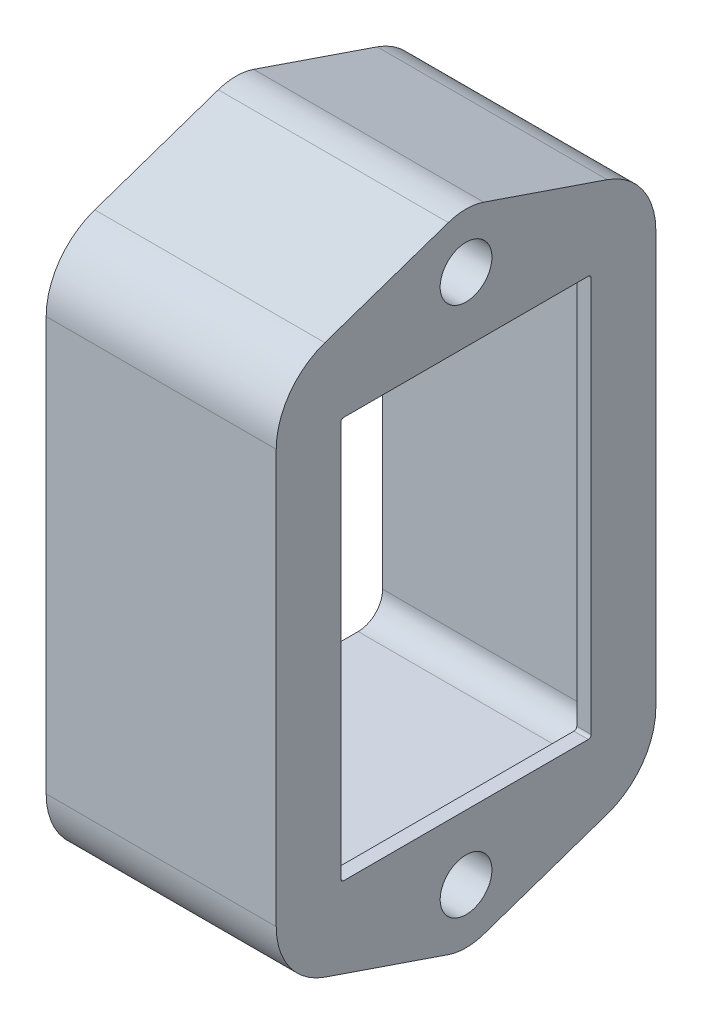
SolidWorks part; units mm, degrees
ref_plane "Alzado" through (0, 0, 0) normal (0, 0, 1) x (1, 0, 0)
ref_plane "Planta" through (0, 0, 0) normal (0, 1, 0) x (1, 0, 0)
ref_plane "Vista lateral" through (0, 0, 0) normal (1, 0, 0) x (0, 0, -1)
sketch "Croquis2" plane through (0, 0, 0) normal (1, 0, 0) x (0, 0, -1)
  line L0 (0, -55.062) -> (0, 49.3875) construction
  line L1 (-26.4, -41.4649) -> (-26.4, 16.0397)
  line L2 (-19.6372, 25.5012) -> (-2.4603, 31.3781)
  line L3 (19.6372, 25.5012) -> (2.4603, 31.3781)
  line L4 (26.4, -41.4649) -> (26.4, 16.0397)
  line L5 (19.6372, -50.9265) -> (2.4603, -56.8034)
  line L6 (20, -40.2126) -> (20, 14.7874) construction
  line L7 (17, 17.7874) -> (0, 17.7874) construction
  line L8 (0, 17.7874) -> (-17, 17.7874) construction
  line L9 (-20, 14.7874) -> (-20, -40.2126) construction
  line L10 (-17, -43.2126) -> (0, -43.2126) construction
  line L11 (0, -43.2126) -> (17, -43.2126) construction
  line L12 (20.4, -40.2126) -> (20.4, 14.7874)
  line L13 (17, 18.1874) -> (0, 18.1874)
  line L14 (0, 18.1874) -> (-17, 18.1874)
  line L15 (-20.4, 14.7874) -> (-20.4, -40.2126)
  line L16 (-17, -43.6126) -> (0, -43.6126)
  line L17 (0, -43.6126) -> (17, -43.6126)
  line L18 (-19.6372, -50.9265) -> (-2.4603, -56.8034)
  line L19 (-39.7632, -12.7126) -> (39.8458, -12.7126) construction
  circle A0 centre (0, 24.1874) radius 3.6
  arc A1 (2.4603, 31.3781) -> (-2.4603, 31.3781) centre (0, 24.1874) ccw
  arc A2 (-19.6372, 25.5012) -> (-26.4, 16.0397) centre (-16.4, 16.0397) ccw
  arc A3 (19.6372, 25.5012) -> (26.4, 16.0397) centre (16.4, 16.0397) cw
  arc A4 (20, 14.7874) -> (17, 17.7874) centre (17, 14.7874) ccw construction
  arc A5 (-17, 17.7874) -> (-20, 14.7874) centre (-17, 14.7874) ccw construction
  arc A6 (-20, -40.2126) -> (-17, -43.2126) centre (-17, -40.2126) ccw construction
  arc A7 (17, -43.2126) -> (20, -40.2126) centre (17, -40.2126) ccw construction
  arc A8 (20.4, 14.7874) -> (17, 18.1874) centre (17, 14.7874) ccw
  arc A9 (-17, 18.1874) -> (-20.4, 14.7874) centre (-17, 14.7874) ccw
  arc A10 (-20.4, -40.2126) -> (-17, -43.6126) centre (-17, -40.2126) ccw
  arc A11 (17, -43.6126) -> (20.4, -40.2126) centre (17, -40.2126) ccw
  circle A12 centre (0, -49.6126) radius 3.6
  arc A13 (2.4603, -56.8034) -> (-2.4603, -56.8034) centre (0, -49.6126) cw
  arc A14 (19.6372, -50.9265) -> (26.4, -41.4649) centre (16.4, -41.4649) ccw
  arc A15 (-19.6372, -50.9265) -> (-26.4, -41.4649) centre (-16.4, -41.4649) cw
  point P36 (-20.4, -12.7126)
  point P43 (-26.4, 23.1874)
  point P53 (26.4, -12.7126)
  point P58 (-26.4, -12.7126)
  dimension "D5" = 7.2
  dimension "D2" = 4
  dimension "D7" = 10
  dimension "D3" = 6
  dimension "D4" = 6
  dimension "D6" = 5
  dimension "D1" = 0.4
extrude "Saliente-Extruir1" add sketch "Croquis2" against normal blind 30 and the other way blind 2
sketch "Croquis3" plane through (2, 0, 0) normal (1, 0, 0) x (0, 0, -1)
  line L0 (-17, -43.6126) -> (17, -43.6126) construction
  line L1 (20.4, -40.2126) -> (20.4, 14.7874) construction
  line L2 (-20.4, 14.7874) -> (-20.4, -40.2126) construction
  line L3 (17, 18.1874) -> (-17, 18.1874) construction
  line L4 (-17, -43.6126) -> (17, -43.6126)
  line L5 (20.4, -40.2126) -> (20.4, 14.7874)
  line L6 (-20.4, 14.7874) -> (-20.4, -40.2126)
  line L7 (17, 18.1874) -> (-17, 18.1874)
  line L8 (-17, -40.6126) -> (17, -40.6126)
  line L9 (17.4, -40.2126) -> (17.4, 14.7874)
  line L10 (17, 15.1874) -> (-17, 15.1874)
  line L11 (-17.4, 14.7874) -> (-17.4, -40.2126)
  arc A0 (-20.4, -40.2126) -> (-17, -43.6126) centre (-17, -40.2126) ccw construction
  arc A1 (17, -43.6126) -> (20.4, -40.2126) centre (17, -40.2126) ccw construction
  arc A2 (20.4, 14.7874) -> (17, 18.1874) centre (17, 14.7874) ccw construction
  arc A3 (-17, 18.1874) -> (-20.4, 14.7874) centre (-17, 14.7874) ccw construction
  arc A4 (-20.4, -40.2126) -> (-17, -43.6126) centre (-17, -40.2126) ccw
  arc A5 (17, -43.6126) -> (20.4, -40.2126) centre (17, -40.2126) ccw
  arc A6 (20.4, 14.7874) -> (17, 18.1874) centre (17, 14.7874) ccw
  arc A7 (-17, 18.1874) -> (-20.4, 14.7874) centre (-17, 14.7874) ccw
  arc A8 (17, -40.6126) -> (17.4, -40.2126) centre (17, -40.2126) ccw
  arc A9 (17.4, 14.7874) -> (17, 15.1874) centre (17, 14.7874) ccw
  arc A10 (-17, 15.1874) -> (-17.4, 14.7874) centre (-17, 14.7874) ccw
  arc A11 (-17.4, -40.2126) -> (-17, -40.6126) centre (-17, -40.2126) ccw
  dimension "D1" = 3
extrude "Saliente-Extruir2" add sketch "Croquis3" against normal blind 2
sketch "Croquis4" plane through (-30, 0, 0) normal (-1, 0, 0) x (0, 0, 1)
  line L0 (20.4, 14.7874) -> (20.4, -40.2126) construction
  line L1 (26.4, 16.0397) -> (26.4, -41.4649) construction
  line L2 (20.4, 14.7874) -> (20.4, -40.2126) construction
  line L3 (26.4, 16.0397) -> (26.4, -41.4649) construction
